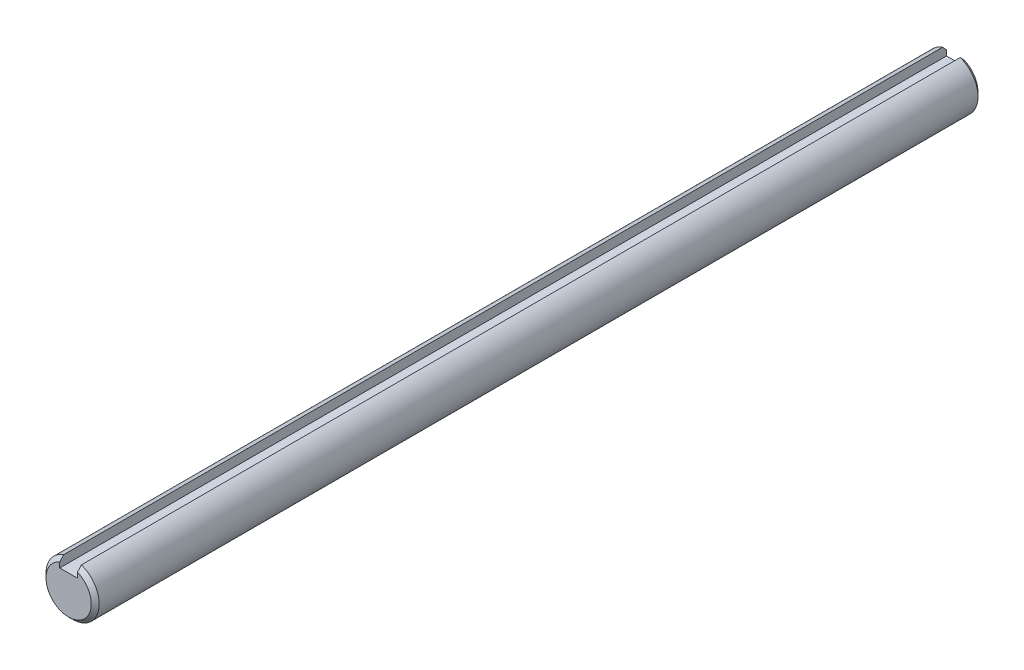
SolidWorks part; units mm, degrees
ref_plane "Front" through (0, 0, 0) normal (0, 0, 1) x (1, 0, 0)
ref_plane "Top" through (0, 0, 0) normal (0, 1, 0) x (1, 0, 0)
ref_plane "Right" through (0, 0, 0) normal (1, 0, 0) x (0, 0, -1)
sketch "Sketch1" plane through (0, 0, 0) normal (0, 0, 1) x (1, 0, 0)
  circle A0 centre (0, 0) radius 6
  dimension "dia" = 12
extrude "Extrude1" add sketch "Sketch1" along normal mid plane 200
sketch "Sketch2" plane through (0, 0, 0) normal (1, 0, 0) x (0, 0, -1)
  point P0 (-100, 6)
  point P1 (100, 6)
  point P2 (100, -6)
chamfer "Chamfer1" distance 0.9 angle 45 2 edges at (6, 0, -100) (6, 0, 100)
sketch "Sketch3" plane through (0, 0, 0) normal (0, 0, 1) x (1, 0, 0)
  line L1 (-2, 6) -> (2, 6)
  line L2 (-2, 6) -> (-2, 3.5)
  line L3 (-2, 3.5) -> (2, 3.5)
  line L4 (2, 6) -> (2, 3.5)
  dimension "key wd" = 4
  dimension "key dp" = 2.5
extrude "Extrude2" cut sketch "Sketch3" against normal through all and the other way through all
ref_plane "Contact Plane 1" through (0, 3.5, 0) normal (0, 1, 0) x (1, 0, 0)
ref_plane "Contact Plane 2" through (0, 0, 100) normal (0, 0, 1) x (1, 0, 0)
ref_plane "Contact Plane 3" through (0, 0, -100) normal (0, 0, -1) x (-1, 0, 0)
ref_axis "Center Axis 1" through (0, 0, 110) along (0, 0, -1)
equation "\"D1@Chamfer1\" = \"dia@Sketch1\" * .075"
